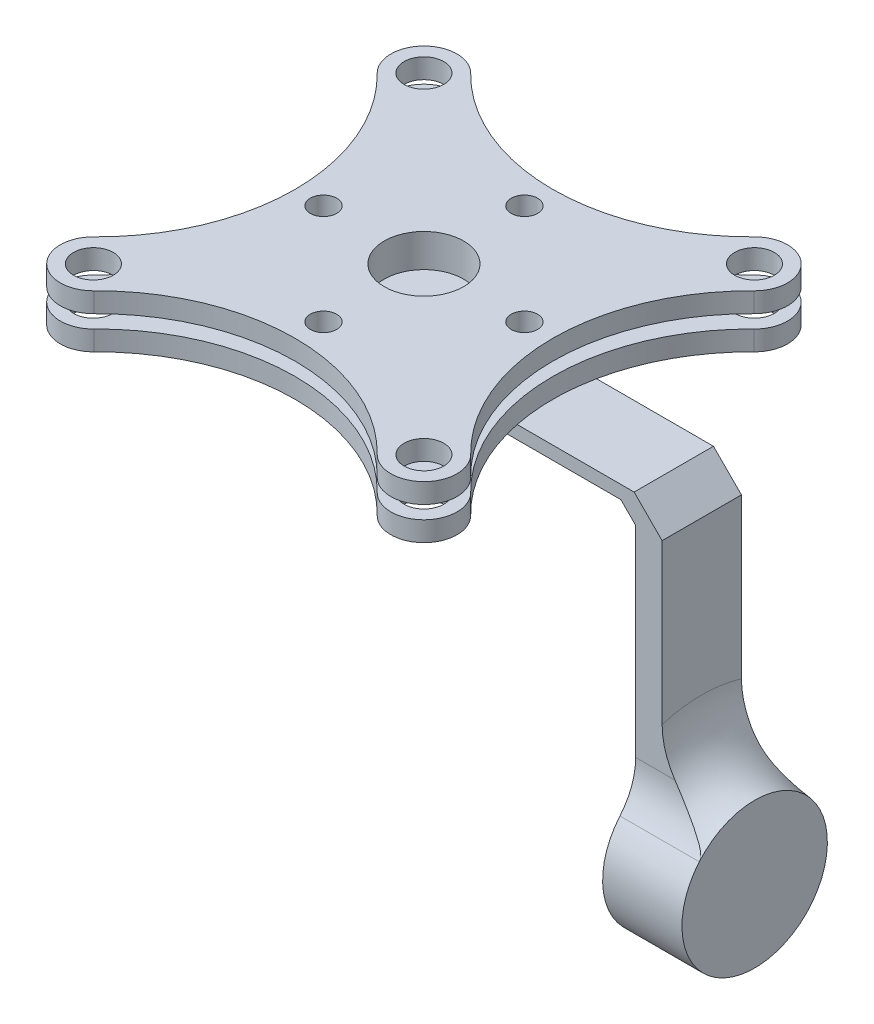
SolidWorks part; units mm, degrees
ref_plane "Front Plane" through (0, 0, 0) normal (0, 0, 1) x (1, 0, 0)
ref_plane "Top Plane" through (0, 0, 0) normal (0, 1, 0) x (1, 0, 0)
ref_plane "Right Plane" through (0, 0, 0) normal (1, 0, 0) x (0, 0, -1)
sketch "Sketch1" plane through (0, 0, 0) normal (0, 1, 0) x (1, 0, 0)
  circle A0 centre (0, 0) radius 27.5
  dimension "D1" = 55
extrude "Boss-Extrude1" add sketch "Sketch1" along normal blind 25
sketch "Sketch24" plane through (0, 25, 0) normal (0, 1, 0) x (1, 0, 0)
  line L0 (-126.9115, 0) -> (101.2807, 0) construction
  line L5 (-71.3388, -71.3388) -> (71.3388, 71.3388) construction
  line L6 (-71.3388, 71.3388) -> (71.3388, -71.3388) construction
  line L7 (0, 83.0143) -> (0, -89.5624) construction
  circle A0 centre (0, 0) radius 27.5
  arc A1 (-53.5714, 71.2482) -> (-71.2482, 53.5714) centre (-62.5, 62.5) ccw
  arc A2 (-53.5714, -71.2482) -> (-71.2482, -53.5714) centre (-62.5, -62.5) cw
  arc A3 (53.5714, 71.2482) -> (71.2482, 53.5714) centre (62.5, 62.5) cw
  arc A4 (53.5714, -71.2482) -> (71.2482, -53.5714) centre (62.5, -62.5) ccw
  arc A5 (-71.2482, -53.5714) -> (-71.2482, 53.5714) centre (-123.7372, 0) ccw
  arc A6 (71.2482, -53.5714) -> (71.2482, 53.5714) centre (123.7372, 0) cw
  arc A7 (53.5714, -71.2482) -> (-53.5714, -71.2482) centre (0, -123.7372) ccw
  arc A8 (53.5714, 71.2482) -> (-53.5714, 71.2482) centre (0, 123.7372) cw
  circle A9 centre (-62.5, 62.5) radius 7.5
  circle A10 centre (-62.5, -62.5) radius 7.5
  circle A11 centre (62.5, -62.5) radius 7.5
  circle A12 centre (62.5, 62.5) radius 7.5
  circle A13 centre (0, 38) radius 5
  circle A14 centre (38, 0) radius 5
  circle A15 centre (0, -38) radius 5
  circle A16 centre (-38, 0) radius 5
  point P42 (0, 0)
  dimension "D1" = 55
  dimension "D4" = 25
  dimension "D5" = 150
  dimension "D2" = 15
  dimension "D3" = 10
  dimension "D6" = 38
  dimension "D7" = 4
extrude "Boss-Extrude7" add sketch "Sketch24" against normal blind 7.5
extrude "Boss-Extrude8" add sketch "Sketch24<2>" against normal blind 7.5 from offset 12.5 offset against normal yes
sketch "Sketch24<2>" plane through (0, 25, 0) normal (0, 1, 0) x (1, 0, 0) same geometry as "Sketch24"
sketch "Sketch25" plane through (0, 25, 0) normal (0, 1, 0) x (1, 0, 0)
  circle A0 centre (0, 0) radius 15
  dimension "D1" = 30
extrude "Cut-Extrude6" cut sketch "Sketch25" against normal blind 12.5
sketch "Sketch9" plane through (0, 0, 0) normal (1, 0, 0) x (0, 0, -1)
  line L0 (-27.5, 0) -> (27.5, 0) construction
  line L1 (-15, 0) -> (15, 0)
  line L2 (-15, 0) -> (-15, 5)
  line L3 (-15, 5) -> (15, 5)
  line L4 (15, 0) -> (15, 5)
  dimension "D1" = 15
  dimension "D2" = 30
  dimension "D3" = 5
extrude "Boss-Extrude3" add sketch "Sketch9" along normal blind 94.49
sketch "Sketch32" plane through (0, 0, 15) normal (0, 0, 1) x (1, 0, 0)
  line L0 (94.49, 5) -> (94.49, 0)
  line L1 (94.49, 0) -> (89.4664, 0)
  line L2 (94.49, 0) -> (23.0489, 0) construction
  line L3 (89.4664, 0) -> (94.49, 5)
extrude "Cut-Extrude10" cut sketch "Sketch32" against normal blind 32
sketch "Sketch33" plane through (44.5229, -44.7327, 0) normal (0.7054, -0.7088, 0) x (0.7088, 0.7054, 0)
  line L4 (70.4986, -15) -> (70.4986, 15)
  line L5 (70.4986, 15) -> (63.4109, 15)
  line L6 (63.4109, 15) -> (63.4109, -15)
  line L7 (63.4109, -15) -> (70.4986, -15)
  line L8 (70.4986, -15) -> (70.4986, 15)
  line L9 (70.4986, 15) -> (63.4109, 15)
  line L10 (63.4109, 15) -> (63.4109, -15)
  line L11 (63.4109, -15) -> (70.4986, -15)
  dimension "D1" = 0
extrude "Boss-Extrude12" add sketch "Sketch33" along normal blind 15
sketch "Sketch34" plane through (0, 0, 15) normal (0, 0, 1) x (1, 0, 0)
  line L0 (105.0716, -5.6315) -> (95.0715, -5.6315)
  line L1 (100.0481, -10.6315) -> (89.4664, 0) construction
  line L2 (95.0715, -5.6315) -> (100.0481, -10.6315)
  line L3 (100.0481, -10.6315) -> (105.0716, -5.6315)
extrude "Cut-Extrude11" cut sketch "Sketch34" against normal blind 34
sketch "Sketch35" plane through (0, -5.6315, 0) normal (0, -1, 0) x (1, 0, 0)
  line L4 (105.0716, -15) -> (105.0716, 15)
  line L5 (105.0716, 15) -> (95.0715, 15)
  line L6 (95.0715, 15) -> (95.0715, -15)
  line L7 (95.0715, -15) -> (105.0716, -15)
  line L8 (105.0716, -15) -> (105.0716, 15)
  line L9 (105.0716, 15) -> (95.0715, 15)
  line L10 (95.0715, 15) -> (95.0715, -15)
  line L11 (95.0715, -15) -> (105.0716, -15)
  dimension "D1" = 0
extrude "Boss-Extrude13" add sketch "Sketch35" along normal blind 110
sketch "Sketch36" plane through (95.0715, 0, 0) normal (-1, 0, 0) x (0, 0, 1)
  line L0 (15, -115.6315) -> (-15, -115.6315) construction
  circle A0 centre (0, -115.6315) radius 27.5
  dimension "D1" = 55
extrude "Boss-Extrude14" add sketch "Sketch36" against normal blind 30
sketch "Sketch37" plane through (95.0715, 0, 0) normal (-1, 0, 0) x (0, 0, 1)
  circle A0 centre (0, -115.6315) radius 25.5
  dimension "D1" = 51
extrude "Cut-Extrude12" cut sketch "Sketch37" against normal blind 25
fillet "Fillet3" radius 25 5 edges at (23.0489, 2.5, 15) (23.0489, 2.5, -15) (100.0716, -92.5826, 15) (105.0716, -88.1315, 0) (100.0716, -92.5826, -15)
